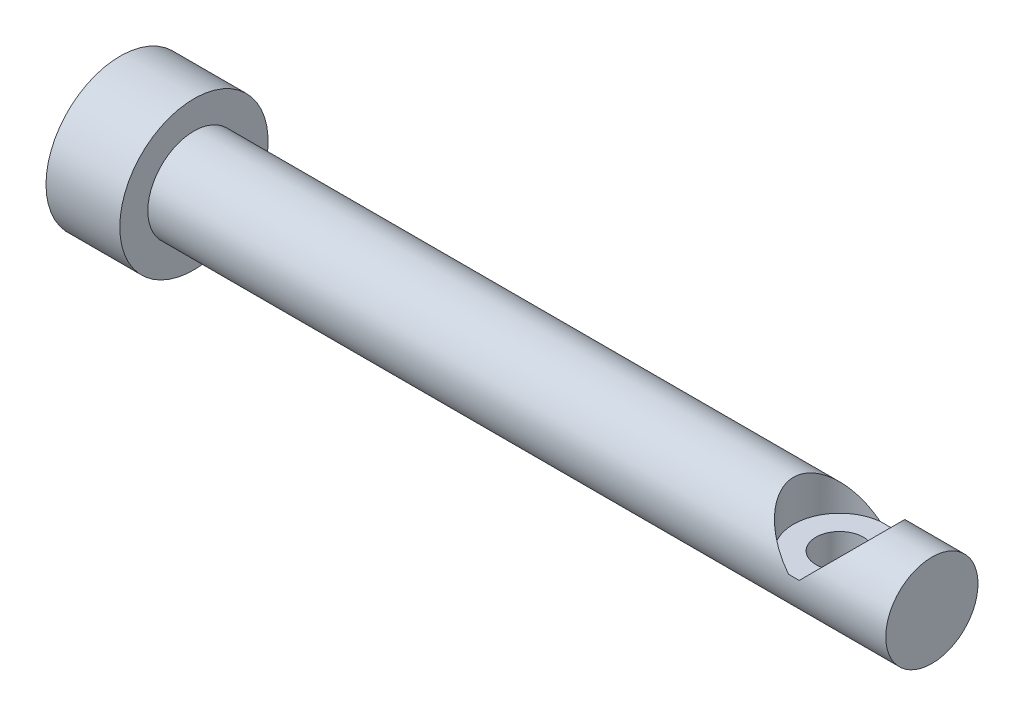
SolidWorks part; units mm, degrees
material "6061-T6 (SS)"
ref_plane "Front Plane" through (0, 0, 0) normal (0, 0, 1) x (1, 0, 0)
ref_plane "Top Plane" through (0, 0, 0) normal (0, 1, 0) x (1, 0, 0)
ref_plane "Right Plane" through (0, 0, 0) normal (1, 0, 0) x (0, 0, -1)
sketch "Sketch1" plane through (0, 0, 0) normal (0, 0, 1) x (1, 0, 0)
  line L0 (-56.203, 40.64) -> (49943.797, 40.64) construction
  line L1 (-46.0375, 40.64) -> (-46.0375, 47.0217)
  line L3 (-46.0375, 47.0217) -> (-39.6875, 47.0217)
  line L4 (-39.6875, 47.0217) -> (-39.6875, 44.6088)
  line L5 (-39.6875, 44.6088) -> (20.6375, 44.6088)
  line L8 (20.6375, 44.6088) -> (20.6375, 40.64)
  line L9 (20.6375, 40.64) -> (-46.0375, 40.64)
  line L10 (15.875, 26.67) -> (15.875, 44.6088) construction
  line L14 (-7.9375, -956.5357) -> (-7.9375, 49043.4643) construction
  line L17 (17.2275, 26.67) -> (14.5225, 26.67) construction
  line L19 (-31.75, 33.655) -> (-6.35, 33.655) construction
  circle A0 centre (-6.35, 33.655) radius 1.5875 construction
  dimension "D5" = 3.175
  dimension "3/16in" = 4.7625
  dimension "D2" = 7.9375
  dimension "D3" = 6.35
  dimension "D4" = 66.675
  dimension "D6" = 31.75
  dimension "D7" = 25.4
revolve "Revolve1" add sketch "Sketch1" angle 360 about L0
ref_plane "Plane1" through (0, 44.6088, 0) normal (0, 1, 0) x (1, 0, 0)
hole_wizard "CBORE for #6 Socket Head Cap Screw1" positions "Sketch5" profile "Sketch6" counterbore size "#6" standard "ANSI Inch" end condition through all
sketch "Sketch5" plane through (0, 44.6088, 0) normal (0, 1, 0) x (1, 0, 0)
  circle A0 centre (15.875, 0) radius 1.3525 construction
  point P0 (15.875, 0)
sketch "Sketch6" plane through (15.875, 44.6088, 0) normal (1, 0, 0) x (0, 0, 1)
  line L0 (0, 0) -> (0, 10.3505)
  line L1 (0, 10.3505) -> (2.0447, 10.3505)
  line L3 (2.0447, 10.3505) -> (2.0447, 3.5052)
  line L4 (2.0447, 3.5052) -> (3.9687, 3.5052)
  line L5 (3.9687, 3.5052) -> (3.9687, 0)
  line L7 (3.9687, 0) -> (0, 0)
  line L11 (0, -6.35) -> (0, 107.95) construction
  dimension "Thru Hole Dia." = 4.0894
  dimension "Thru Hole Depth" = 10.3505
  dimension "C'Bore Dia." = 7.9375
  dimension "C'Bore Depth" = 3.5052
sketch "Sketch7" plane through (20.6375, 0, 0) normal (1, 0, 0) x (0, 0, -1)
  circle A0 centre (0, 40.64) radius 3.9688
  circle A1 centre (0, 40.64) radius 3.9688 construction
extrude "Boss-Extrude1" add sketch "Sketch7" along normal blind 3.175
